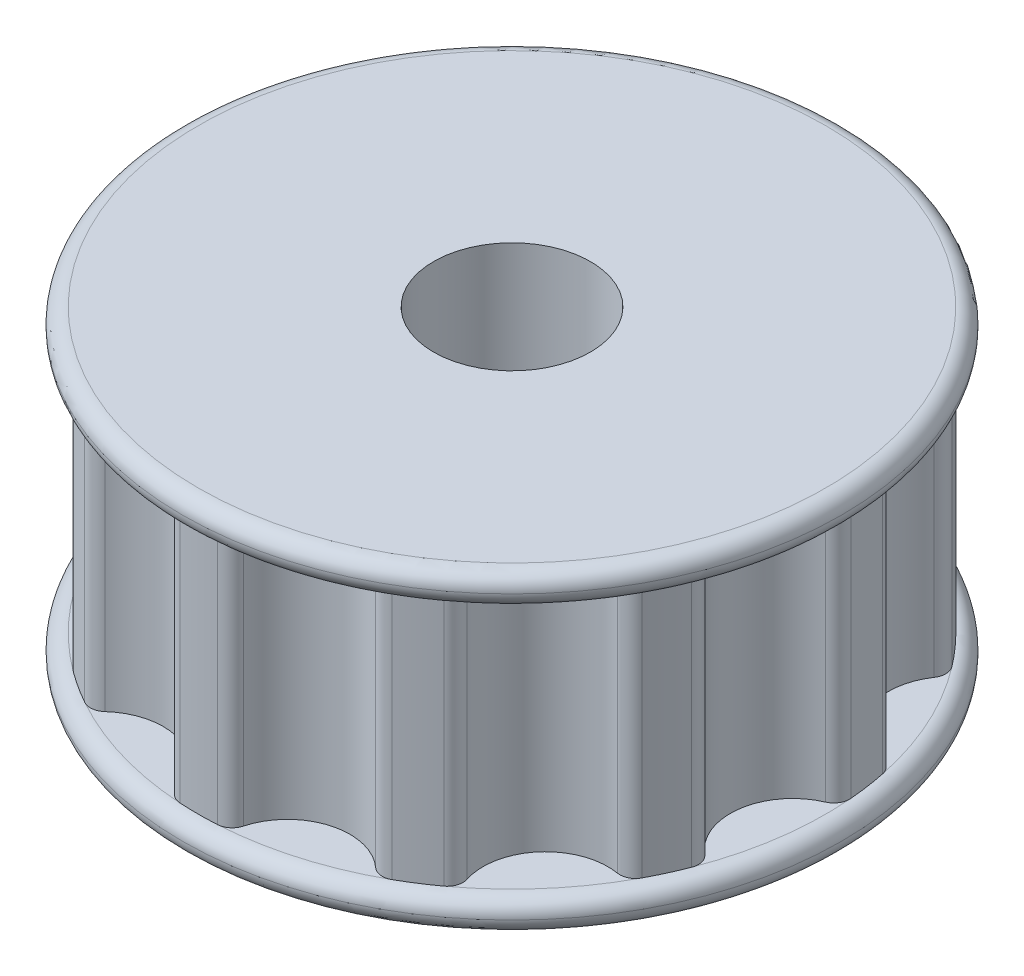
SolidWorks part; units mm, degrees
ref_plane "前视基准面" through (0, 0, 0) normal (0, 0, 1) x (1, 0, 0)
ref_plane "上视基准面" through (0, 0, 0) normal (0, 1, 0) x (1, 0, 0)
ref_plane "右视基准面" through (0, 0, 0) normal (1, 0, 0) x (0, 0, -1)
sketch "草图1" plane through (0, 0, 0) normal (0, 1, 0) x (1, 0, 0)
  line L1 (-1.7, 9.5194) -> (1.7, 9.5194) construction
  arc A0 (-2.2387, 9.7462) -> (-3.3859, 9.4094) centre (0, 0) ccw
  circle A1 centre (0, 0) radius 2.5
  circle A2 centre (0, 0) radius 9.67 construction
  circle A3 centre (0, 0) radius 10.5
  arc A4 (-1.7, 9.5194) -> (1.7, 9.5194) centre (0, 10.5571) ccw
  arc A5 (-2.2387, 9.7462) -> (-1.7, 9.5194) centre (-2.1268, 9.2589) cw
  arc A6 (2.2387, 9.7462) -> (1.7, 9.5194) centre (2.1268, 9.2589) ccw
  arc A7 (3.7164, 8.9273) -> (6.5767, 7.0891) centre (5.7076, 8.8812) ccw
  arc A8 (7.1525, 6.9887) -> (6.5767, 7.0891) centre (6.7949, 6.6392) ccw
  arc A9 (3.3859, 9.4094) -> (3.7164, 8.9273) centre (3.2166, 8.9389) cw
  arc A10 (7.9529, 5.5009) -> (9.3654, 2.4081) centre (9.6031, 4.3856) ccw
  arc A11 (9.7954, 2.0123) -> (9.3654, 2.4081) centre (9.3057, 1.9117) ccw
  arc A12 (7.9355, 6.0851) -> (7.9529, 5.5009) centre (7.5387, 5.7809) cw
  arc A13 (9.6644, 0.3279) -> (9.1806, -3.0374) centre (10.4497, -1.5024) ccw
  arc A14 (9.3284, -3.6029) -> (9.1806, -3.0374) centre (8.862, -3.4228) ccw
  arc A15 (9.9656, 0.8289) -> (9.6644, 0.3279) centre (9.4673, 0.7874) cw
  arc A16 (8.3075, -4.9491) -> (6.081, -7.5187) centre (7.9786, -6.9135) ccw
  arc A17 (5.8996, -8.0743) -> (6.081, -7.5187) centre (5.6047, -7.6706) ccw
  arc A18 (8.8317, -4.6905) -> (8.3075, -4.9491) centre (8.3901, -4.456) cw
  arc A19 (4.3131, -8.6548) -> (1.0508, -9.6127) centre (2.9743, -10.1295) ccw
  arc A20 (0.5978, -9.9821) -> (1.0508, -9.6127) centre (0.5679, -9.483) ccw
  arc A21 (4.8938, -8.7207) -> (4.3131, -8.6548) centre (4.6491, -8.2847) cw
  arc A22 (-1.0508, -9.6127) -> (-4.3131, -8.6548) centre (-2.9743, -10.1295) ccw
  arc A23 (-4.8938, -8.7207) -> (-4.3131, -8.6548) centre (-4.6491, -8.2847) ccw
  arc A24 (-0.5978, -9.9821) -> (-1.0508, -9.6127) centre (-0.5679, -9.483) cw
  arc A25 (-6.081, -7.5187) -> (-8.3075, -4.9491) centre (-7.9786, -6.9135) ccw
  arc A26 (-8.8317, -4.6905) -> (-8.3075, -4.9491) centre (-8.3901, -4.456) ccw
  arc A27 (-5.8996, -8.0743) -> (-6.081, -7.5187) centre (-5.6047, -7.6706) cw
  arc A28 (-9.1806, -3.0374) -> (-9.6644, 0.3279) centre (-10.4497, -1.5024) ccw
  arc A29 (-9.9656, 0.8289) -> (-9.6644, 0.3279) centre (-9.4673, 0.7874) ccw
  arc A30 (-9.3284, -3.6029) -> (-9.1806, -3.0374) centre (-8.862, -3.4228) cw
  arc A31 (-9.3654, 2.4081) -> (-7.9529, 5.5009) centre (-9.6031, 4.3856) ccw
  arc A32 (-7.9355, 6.0851) -> (-7.9529, 5.5009) centre (-7.5387, 5.7809) ccw
  arc A33 (-9.7954, 2.0123) -> (-9.3654, 2.4081) centre (-9.3057, 1.9117) cw
  arc A34 (-6.5767, 7.0891) -> (-3.7164, 8.9273) centre (-5.7076, 8.8812) ccw
  arc A35 (-3.3859, 9.4094) -> (-3.7164, 8.9273) centre (-3.2166, 8.9389) ccw
  arc A36 (-7.1525, 6.9887) -> (-6.5767, 7.0891) centre (-6.7949, 6.6392) cw
  arc A37 (3.3859, 9.4094) -> (2.2387, 9.7462) centre (0, 0) ccw
  arc A38 (7.9355, 6.0851) -> (7.1525, 6.9887) centre (0, 0) ccw
  arc A39 (9.9656, 0.8289) -> (9.7954, 2.0123) centre (0, 0) ccw
  arc A40 (8.8317, -4.6905) -> (9.3284, -3.6029) centre (0, 0) ccw
  arc A41 (4.8938, -8.7207) -> (5.8996, -8.0743) centre (0, 0) ccw
  arc A42 (-0.5978, -9.9821) -> (0.5978, -9.9821) centre (0, 0) ccw
  arc A43 (-5.8996, -8.0743) -> (-4.8938, -8.7207) centre (0, 0) ccw
  arc A44 (-9.3284, -3.6029) -> (-8.8317, -4.6905) centre (0, 0) ccw
  arc A45 (-9.7954, 2.0123) -> (-9.9656, 0.8289) centre (0, 0) ccw
  arc A46 (-7.1525, 6.9887) -> (-7.9355, 6.0851) centre (0, 0) ccw
  dimension "D1" = 5
  dimension "D2" = 19.34
  dimension "D3" = 20
  dimension "D4" = 21
  dimension "D5" = 0.5
  dimension "D6" = 0.5
  dimension "D7" = 3.4
extrude "凸台-拉伸3" add sketch "草图1" along normal blind 8 contours A4 A6 A37 A9 A7 A8 A38 A12 A10 A11 A39 A15 A13 A14 A40 A18 A16 A17 A41 A21 A19 A20 A42 A24 A22 A23 A43 A27 A25 A26 A44 A30 A28 A29 A45 A33 A31 A32 A46 A36 A34 A35 A0 A5
sketch "草图4" plane through (0, 0, 0) normal (0, -1, 0) x (1, 0, 0)
  circle A0 centre (0, 0) radius 10.5
  dimension "D1" = 21
extrude "凸台-拉伸4" add sketch "草图4" along normal blind 1
sketch "草图5" plane through (0, 8, 0) normal (0, 1, 0) x (1, 0, 0)
  circle A0 centre (0, 0) radius 10.5
extrude "凸台-拉伸5" add sketch "草图5" along normal blind 1
fillet "圆角1" radius 0.5 2 edges at (0, 0, -10.5) (0, -1, -10.5)
fillet "圆角2" radius 0.5 2 edges at (0, 8, 10.5) (0, 9, 10.5)
sketch "草图6" plane through (0, 9, 0) normal (0, 1, 0) x (1, 0, 0)
  circle A0 centre (0, 0) radius 2.5
  dimension "D1" = 5
extrude "切除-拉伸1" cut sketch "草图6" against normal through all
ref_axis "基准轴1" through (0, -0.4706, 0) along (0, 1, 0)
ref_plane "基准面1" through (0, 0, -10) normal (0, 0, 1) x (1, 0, 0)
sketch "草图15" plane through (0, 0, -10) normal (0, 0, 1) x (1, 0, 0)
  line L0 (0, -0.4706) -> (0, 9.5294) construction
  circle A0 centre (0, 4.2164) radius 1.5
  dimension "D1" = 3
extrude "切除-拉伸3" cut sketch "草图15" along normal blind 9
